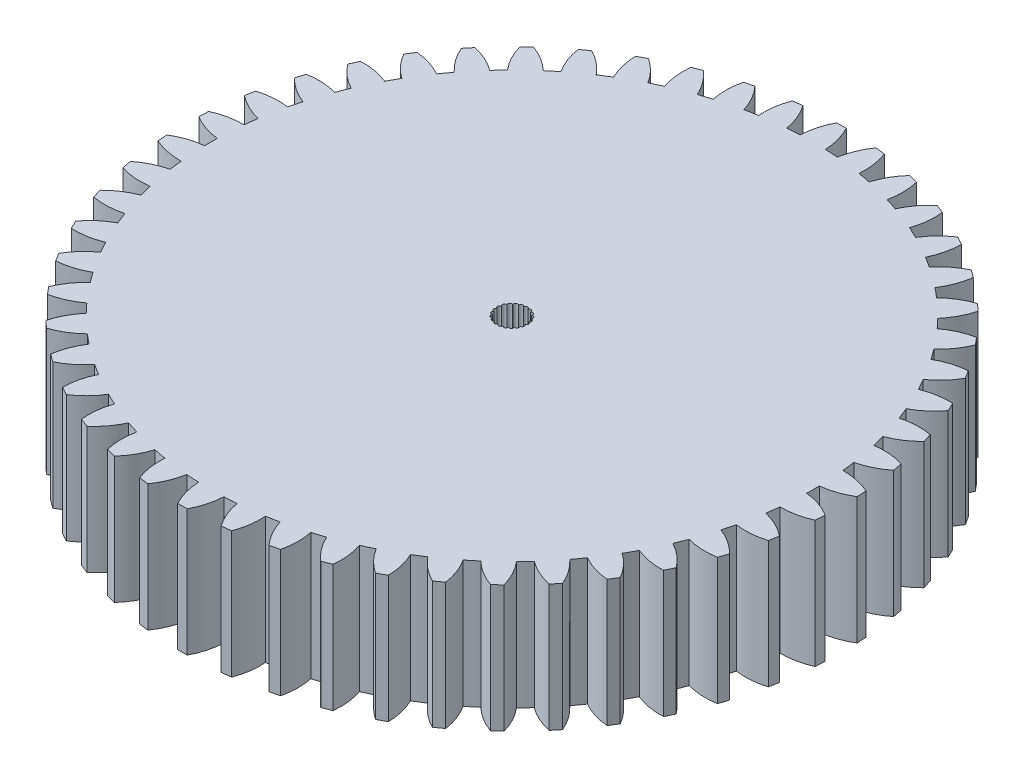
SolidWorks part; units mm, degrees
ref_plane "Front Plane" through (0, 0, 0) normal (0, 0, 1) x (1, 0, 0)
ref_plane "Top Plane" through (0, 0, 0) normal (0, 1, 0) x (1, 0, 0)
ref_plane "Right Plane" through (0, 0, 0) normal (1, 0, 0) x (0, 0, -1)
sketch "Sketch2" plane through (0, 0, 0) normal (0, 1, 0) x (1, 0, 0)
  line L0 (0, -10.2886) -> (0, 10.2886) construction
  line L1 (0, 0) -> (0.6267, 4.1579) construction
  line L2 (0, 0) -> (-0.6267, 4.1579) construction
  line L3 (0, 0) -> (0.5497, 17.4914) construction
  line L4 (0, 0) -> (-0.5497, 17.4914) construction
  line L7 (-0.75, 51.9946) -> (0.75, 51.9946)
  line L9 (7.8676, 46.3212) -> (7.9539, 46.8293)
  line L10 (3.8992, 46.8226) -> (3.9419, 47.3362)
  line L12 (13.6112, 44.9699) -> (13.7605, 45.4632)
  line L13 (9.7368, 45.9647) -> (9.8436, 46.4688)
  line L15 (19.1401, 42.9094) -> (19.35, 43.38)
  line L16 (15.421, 44.3819) -> (15.5901, 44.8687)
  line L18 (24.3671, 40.1721) -> (24.6344, 40.6128)
  line L19 (20.8619, 42.0991) -> (21.0907, 42.5609)
  line L21 (29.2099, 36.8013) -> (29.5303, 37.205)
  line L22 (25.9738, 39.1525) -> (26.2587, 39.5819)
  line L24 (33.592, 32.8502) -> (33.9604, 33.2105)
  line L25 (30.6761, 35.5884) -> (31.0126, 35.9787)
  line L27 (37.4443, 28.381) -> (37.855, 28.6923)
  line L28 (34.8946, 31.463) -> (35.2774, 31.8081)
  line L30 (40.7061, 23.4641) -> (41.1526, 23.7215)
  line L31 (38.5628, 26.8415) -> (38.9858, 27.1359)
  line L33 (43.326, 18.1773) -> (43.8012, 18.3767)
  line L34 (41.6229, 21.7966) -> (42.0794, 22.0357)
  line L36 (45.2626, 12.6038) -> (45.7591, 12.742)
  line L37 (44.0265, 16.408) -> (44.5094, 16.588)
  line L39 (46.4853, 6.8315) -> (46.9952, 6.9064)
  line L40 (45.7358, 10.7606) -> (46.2375, 10.8787)
  line L42 (46.975, 0.9515) -> (47.4903, 0.9619)
  line L43 (46.7238, 4.9436) -> (47.2363, 4.9978)
  line L45 (46.7238, -4.9436) -> (47.2363, -4.9978)
  line L46 (46.975, -0.9515) -> (47.4903, -0.9619)
  line L48 (45.7358, -10.7606) -> (46.2375, -10.8787)
  line L49 (46.4853, -6.8315) -> (46.9952, -6.9064)
  line L51 (44.0265, -16.408) -> (44.5094, -16.588)
  line L52 (45.2626, -12.6038) -> (45.7591, -12.742)
  line L54 (41.6229, -21.7966) -> (42.0794, -22.0357)
  line L55 (43.326, -18.1773) -> (43.8012, -18.3767)
  line L57 (38.5628, -26.8415) -> (38.9858, -27.1359)
  line L58 (40.7061, -23.4641) -> (41.1526, -23.7215)
  line L60 (34.8946, -31.463) -> (35.2774, -31.8081)
  line L61 (37.4443, -28.381) -> (37.855, -28.6923)
  line L63 (30.6761, -35.5884) -> (31.0126, -35.9787)
  line L64 (33.592, -32.8502) -> (33.9604, -33.2105)
  line L66 (25.9738, -39.1525) -> (26.2587, -39.5819)
  line L67 (29.2099, -36.8013) -> (29.5303, -37.205)
  line L69 (20.8619, -42.0991) -> (21.0907, -42.5609)
  line L70 (24.3671, -40.1721) -> (24.6344, -40.6128)
  line L72 (15.421, -44.3819) -> (15.5901, -44.8687)
  line L73 (19.1401, -42.9094) -> (19.35, -43.38)
  line L75 (9.7368, -45.9647) -> (9.8436, -46.4688)
  line L76 (13.6112, -44.9699) -> (13.7605, -45.4632)
  line L78 (3.8992, -46.8226) -> (3.9419, -47.3362)
  line L79 (7.8676, -46.3212) -> (7.9539, -46.8293)
  line L81 (-2, -46.942) -> (-2.0219, -47.4569)
  line L82 (2, -46.942) -> (2.0219, -47.4569)
  line L84 (-7.8676, -46.3212) -> (-7.9539, -46.8293)
  line L85 (-3.8992, -46.8226) -> (-3.9419, -47.3362)
  line L87 (-13.6112, -44.9699) -> (-13.7605, -45.4632)
  line L88 (-9.7368, -45.9647) -> (-9.8436, -46.4688)
  line L90 (-19.1401, -42.9094) -> (-19.35, -43.38)
  line L91 (-15.421, -44.3819) -> (-15.5901, -44.8687)
  line L93 (-24.3671, -40.1721) -> (-24.6344, -40.6128)
  line L94 (-20.8619, -42.0991) -> (-21.0907, -42.5609)
  line L96 (-29.2099, -36.8013) -> (-29.5303, -37.205)
  line L97 (-25.9738, -39.1525) -> (-26.2587, -39.5819)
  line L99 (-33.592, -32.8502) -> (-33.9604, -33.2105)
  line L100 (-30.6761, -35.5884) -> (-31.0126, -35.9787)
  line L102 (-37.4443, -28.381) -> (-37.855, -28.6923)
  line L103 (-34.8946, -31.463) -> (-35.2774, -31.8081)
  line L105 (-40.7061, -23.4641) -> (-41.1526, -23.7215)
  line L106 (-38.5628, -26.8415) -> (-38.9858, -27.1359)
  line L108 (-43.326, -18.1773) -> (-43.8012, -18.3767)
  line L109 (-41.6229, -21.7966) -> (-42.0794, -22.0357)
  line L111 (-45.2626, -12.6038) -> (-45.7591, -12.742)
  line L112 (-44.0265, -16.408) -> (-44.5094, -16.588)
  line L114 (-46.4853, -6.8315) -> (-46.9952, -6.9064)
  line L115 (-45.7358, -10.7606) -> (-46.2375, -10.8787)
  line L117 (-46.975, -0.9515) -> (-47.4903, -0.9619)
  line L118 (-46.7238, -4.9436) -> (-47.2363, -4.9978)
  line L120 (-46.7238, 4.9436) -> (-47.2363, 4.9978)
  line L121 (-46.975, 0.9515) -> (-47.4903, 0.9619)
  line L123 (-45.7358, 10.7606) -> (-46.2375, 10.8787)
  line L124 (-46.4853, 6.8315) -> (-46.9952, 6.9064)
  line L126 (-44.0265, 16.408) -> (-44.5094, 16.588)
  line L127 (-45.2626, 12.6038) -> (-45.7591, 12.742)
  line L129 (-41.6229, 21.7966) -> (-42.0794, 22.0357)
  line L130 (-43.326, 18.1773) -> (-43.8012, 18.3767)
  line L132 (-38.5628, 26.8415) -> (-38.9858, 27.1359)
  line L133 (-40.7061, 23.4641) -> (-41.1526, 23.7215)
  line L135 (-34.8946, 31.463) -> (-35.2774, 31.8081)
  line L136 (-37.4443, 28.381) -> (-37.855, 28.6923)
  line L138 (-30.6761, 35.5884) -> (-31.0126, 35.9787)
  line L139 (-33.592, 32.8502) -> (-33.9604, 33.2105)
  line L141 (-25.9738, 39.1525) -> (-26.2587, 39.5819)
  line L142 (-29.2099, 36.8013) -> (-29.5303, 37.205)
  line L144 (-20.8619, 42.0991) -> (-21.0907, 42.5609)
  line L145 (-24.3671, 40.1721) -> (-24.6344, 40.6128)
  line L147 (-15.421, 44.3819) -> (-15.5901, 44.8687)
  line L148 (-19.1401, 42.9094) -> (-19.35, 43.38)
  line L150 (-9.7368, 45.9647) -> (-9.8436, 46.4688)
  line L151 (-13.6112, 44.9699) -> (-13.7605, 45.4632)
  line L153 (-3.8992, 46.8226) -> (-3.9419, 47.3362)
  line L154 (-7.8676, 46.3212) -> (-7.9539, 46.8293)
  circle A0 centre (0, 0) radius 46.9846 construction
  circle A1 centre (0, 0) radius 2.2
  circle A2 centre (0, 0) radius 2.45 construction
  arc A3 (-0.3279, 2.1754) -> (0.3279, 2.1754) centre (0, 2.1169) cw
  arc A4 (0.3279, 2.1754) -> (0.9545, 1.9821) centre (0.624, 2.0229) cw
  arc A5 (0.9545, 1.9821) -> (1.4964, 1.6127) centre (1.1925, 1.7491) cw
  arc A6 (1.4964, 1.6127) -> (1.9053, 1.1) centre (1.6551, 1.3199) cw
  arc A7 (1.9053, 1.1) -> (2.1448, 0.4895) centre (1.9706, 0.7734) cw
  arc A8 (2.1448, 0.4895) -> (2.1938, -0.1644) centre (2.111, 0.1582) cw
  arc A9 (2.1938, -0.1644) -> (2.0479, -0.8038) centre (2.0639, -0.4711) cw
  arc A10 (2.0479, -0.8038) -> (1.72, -1.3717) centre (1.8333, -1.0585) cw
  arc A11 (1.72, -1.3717) -> (1.2393, -1.8177) centre (1.4399, -1.5518) cw
  arc A12 (1.2393, -1.8177) -> (0.6485, -2.1023) centre (0.9185, -1.9073) cw
  arc A13 (0.6485, -2.1023) -> (0, -2.2) centre (0.3155, -2.0933) cw
  arc A14 (0, -2.2) -> (-0.6485, -2.1023) centre (-0.3155, -2.0933) cw
  arc A15 (-0.6485, -2.1023) -> (-1.2393, -1.8177) centre (-0.9185, -1.9073) cw
  arc A16 (-1.2393, -1.8177) -> (-1.72, -1.3717) centre (-1.4399, -1.5518) cw
  arc A17 (-1.72, -1.3717) -> (-2.0479, -0.8038) centre (-1.8333, -1.0585) cw
  arc A18 (-2.0479, -0.8038) -> (-2.1938, -0.1644) centre (-2.0639, -0.4711) cw
  arc A19 (-2.1938, -0.1644) -> (-2.1448, 0.4895) centre (-2.111, 0.1582) cw
  arc A20 (-2.1448, 0.4895) -> (-1.9053, 1.1) centre (-1.9706, 0.7734) cw
  arc A21 (-1.9053, 1.1) -> (-1.4964, 1.6127) centre (-1.6551, 1.3199) cw
  arc A22 (-1.4964, 1.6127) -> (-0.9545, 1.9821) centre (-1.1925, 1.7491) cw
  arc A23 (-0.9545, 1.9821) -> (-0.3279, 2.1754) centre (-0.624, 2.0229) cw
  circle A24 centre (0, 0) radius 47.5
  circle A25 centre (0, 0) radius 50 construction
  circle A26 centre (0, 0) radius 52 construction
  arc A27 (0.75, 51.9946) -> (2, 46.942) centre (-8.7153, 46.972) cw
  arc A28 (-0.75, 51.9946) -> (-2, 46.942) centre (8.7153, 46.972) ccw
  point P7 (0, 0)
  point P30 (1.5705, 49.9753)
  point P78 (0, 0)
  point P226 (0, 0)
  dimension "D1" = 4.4
  dimension "D3" = 4.9
  dimension "D5" = 93.9693
  dimension "D6" = 95
  dimension "D7" = 100
  dimension "D8" = 104
  dimension "D2" = 8.571
  dimension "D9" = 1.8
  dimension "D11" = 1.5
  dimension "D12" = 4
  dimension "D4" = 21
extrude "Boss-Extrude1" add sketch "Sketch2" along normal blind 20 contours A24 L154 L150 L151 L147 L148 L144 L145 L141 L142 L138 L139 L135 L136 L132 L133 L129 region at (0, 0, -46.1565)
extrude "Boss-Extrude2" add sketch "Sketch2<4>" along normal up to surface (20 mm away) contours L7 A28 A24 A27 region at (0, 0, -49.443) up to face at (0, 20, 47.5)
sketch "Sketch2<4>" plane through (0, 0, 0) normal (0, 1, 0) x (1, 0, 0) same geometry as "Sketch2"
pattern_circular "CirPattern1" count 50 over 360 about axis through (0, 20, 0) along (0, 1, 0) of "Boss-Extrude2"
equation "\"Module\"= 2"
equation "\"Teeth\"= 50"
equation "\"Pitch Diameter\"= \"Module\" * \"Teeth\""
equation "\"Outer Diamter\"= \"Pitch Diameter\" + ( 2 * \"Module\" )"
equation "\"Root Diameter\"= \"Pitch Diameter\" - ( 2.5 * \"Module\" )"
equation "\"Base Diamter\"= \"Pitch Diameter\" * cos ( 20 )"
equation "\"D5@Sketch2\"=\"Base Diamter\""
equation "\"D6@Sketch2\"=\"Root Diameter\""
equation "\"D8@Sketch2\"=\"Outer Diamter\""
equation "\"D9@Sketch2\"=90 / \"Teeth\""
